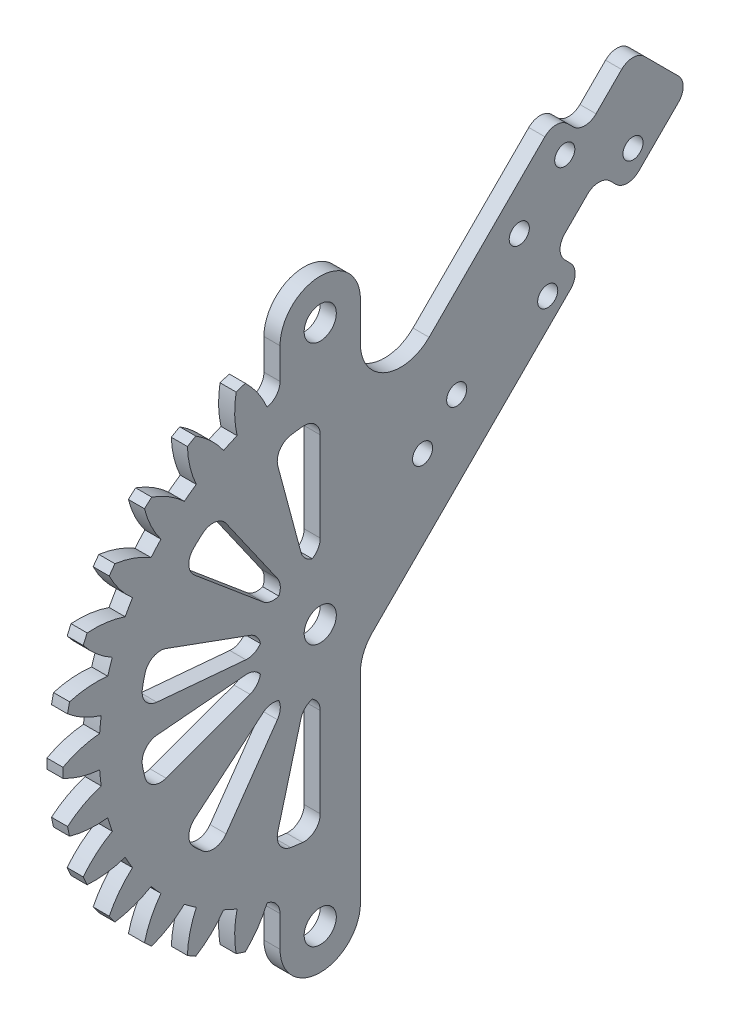
SolidWorks part; units mm, degrees
material "Thornel Mat VMA"
ref_plane "Plane1" through (0, 0, 0) normal (0, 0, 1) x (1, 0, 0)
ref_plane "Plane2" through (0, 0, 0) normal (0, 1, 0) x (1, 0, 0)
ref_plane "Plane3" through (0, 0, 0) normal (1, 0, 0) x (0, 0, -1)
sketch "HoldingSke" plane through (0, 0, 0) normal (0, 1, 0) x (1, 0, 0)
  line L0 (0, 0) -> (0.433, -0.25)
  line L1 (-15, 0) -> (100, 0) construction
  line L2 (0, 0) -> (-2.1039, 2.3779)
  line L3 (0, 0) -> (-11.863, 4.5341)
  line L4 (0, 0) -> (7.479, 4.318)
  line L5 (0, 0) -> (-46.8476, -17.4728)
  line L6 (0, 0) -> (-1.6579, -1.1186)
  line L7 (-2.1039, 2.3779) -> (8.6586, 51.2059)
  line L8 (-76.2, 54.61) -> (-76.1, 54.61)
  line L9 (-71.009, 38.7566) -> (-53.1078, 45.2721)
  line L10 (-76.2, 71.12) -> (104.1128, 71.12)
  line L11 (0, 0) -> (-2, 0)
  line L12 (-76.2, 101.6) -> (-76.133, 101.6)
  line L13 (24.9733, 27.94) -> (52.9518, 28.4284)
  line L14 (24.9733, 27.94) -> (24.9743, 27.94)
  line L15 (24.9733, 27.94) -> (100.4006, 29.5858)
  line L16 (-63.627, -2) -> (-12.827, -2)
  circle A0 centre (0, 0) radius 0.4
  circle A1 centre (0, 0) radius 27.499
  circle A2 centre (0, 0) radius 37.5
  circle A3 centre (0, 0) radius 0.4
  dimension "MHD" = 54.998
  dimension "Hub_dia" = 75
  dimension "Bore" = 0.8
  dimension "MBD" = 0.8
  dimension "Num_teeth" = 30
  dimension "Pitch" = 0.5
  dimension "Overall_len" = 50
  dimension "Show_teeth" = 30
  dimension "Thickness" = 2
  dimension "OAL" = 50.0001
  dimension "T_dim" = 0.1
  dimension "Ap" = 20
  dimension "H" = 19.05
  dimension "Pitch_radius" = 180.3128
  dimension "Width" = 2
  dimension "Backlash" = 0.067
  dimension "Addendum_fac" = 1
  dimension "Dedendum_fac" = 1.25
  dimension "Clearance_fac" = 0.25
  dimension "Dedendum_add" = 0.001
  dimension "Module" = 2
sketch "BasProSke" plane through (0, 0, 0) normal (0, 1, 0) x (1, 0, 0)
  line L0 (-10, 0) -> (60, 0) construction
  line L1 (0, 0) -> (0, 32)
  line L2 (0, 0) -> (2, 0)
  line L3 (2, 0) -> (2, 32)
  line L4 (2, 32) -> (0, 32)
  dimension "Thickness" = 2
  dimension "Diameter" = 64
revolve "Base-Revolve" add sketch "BasProSke" angle 360 about L0
sketch "TooCutSke" plane through (0, 0, 0) normal (1, 0, 0) x (0, 0, -1)
  line L1 (0, 0) -> (0, 107) construction
  line L2 (0, 0) -> (-1.6873, 29.9525) construction
  line L3 (0, 0) -> (-6.2643, 59.6013) construction
  line L4 (-1.6873, 29.9525) -> (-3.1322, 29.8007) construction
  arc A0 (0.9186, 27.4837) -> (-0.9186, 27.4837) centre (0, 0) ccw
  arc A1 (2.7618, 31.9061) -> (-2.7618, 31.9061) centre (0, 0) ccw
  circle A2 centre (0, 0) radius 30 construction
  circle A3 centre (0, 0) radius 28.1908 construction
  arc A4 (-0.9186, 27.4837) -> (-2.7618, 31.9061) centre (-12.6936, 25.1712) ccw
  arc A5 (2.7618, 31.9061) -> (0.9186, 27.4837) centre (12.6936, 25.1712) ccw
  dimension "Root_dia" = 54.998
  dimension "Overcut_dia" = 64.0508
  dimension "Pitch_dia" = 60
  dimension "Base_dia" = 56.3816
  dimension "Flank_rad" = 12
  dimension "Half_ang" = 6
  dimension "Half_CT" = 1.4528
extrude "ToothCut" cut sketch "TooCutSke" along normal through all
fillet "Breaks" [suppressed] radius 0.04 tangent propagation no
fillet "RootFillets" [suppressed] radius 0.501
pattern_circular "TeethCuts" count 30 every 12 about axis through (-10, 0, 0) along (1, 0, 0) of "ToothCut", "RootFillets", "Breaks"
sketch "HubNeaOneSke" plane through (0, 0, 0) normal (-1, 0, 0) x (0, 0, 1)
  circle A0 centre (0, 0) radius 27.499
  dimension "Diameter" = 54.998
extrude "HubNearOne" [suppressed] add sketch "HubNeaOneSke" along normal blind 48.0001
sketch "HubNeaBotSke" plane through (0, 0, 0) normal (-1, 0, 0) x (0, 0, 1)
  circle A0 centre (0, 0) radius 27.499
  dimension "Diameter" = 54.998
extrude "HubNearBoth" [suppressed] add sketch "HubNeaBotSke" along normal blind 24
ref_plane "FarPln" through (2, 0, 0) normal (1, 0, 0) x (0, 0, -1)
sketch "HubFarSke" plane through (2, 0, 0) normal (1, 0, 0) x (0, 0, -1)
  circle A0 centre (0, 0) radius 27.499
  dimension "Diameter" = 54.998
extrude "HubFar" [suppressed] add sketch "HubFarSke" along normal blind 24
sketch "BorSke" plane through (0, 0, 0) normal (1, 0, 0) x (0, 0, -1)
  circle A0 centre (0, 0) radius 0.4
  dimension "Diameter" = 0.8
extrude "Bore" cut sketch "BorSke" along normal mid plane 100.0001
sketch "KeySke" plane through (0, 0, 0) normal (1, 0, 0) x (0, 0, -1)
  line L0 (-0.05, 0) -> (-0.05, 0.5)
  line L1 (-0.05, 0.5) -> (0.05, 0.5)
  line L2 (0.05, 0.5) -> (0.05, 0)
  line L3 (0, 0) -> (0, 34) construction
  line L4 (-0.05, 0) -> (0.05, 0)
  dimension "Offset" = 0.5
  dimension "Width" = 0.1
extrude "Keyway" [suppressed] cut sketch "KeySke" along normal mid plane 100.0001
pattern_circular "Keyway2" [suppressed] count 2 every 90 about axis through (-10, 0, 0) along (1, 0, 0)
sketch "草图1" plane through (2, 0, 0) normal (1, 0, 0) x (0, 0, -1)
  line L0 (0, 36.7097) -> (0, -36.236)
  line L1 (0, -36.236) -> (49.7984, -32.8986)
  line L2 (49.7984, -32.8986) -> (48.3681, 29.8306)
  line L3 (48.3681, 29.8306) -> (0, 36.7097)
extrude "切除-拉伸1" cut sketch "草图1" against normal blind 10
sketch "草图2" plane through (2, 0, 0) normal (1, 0, 0) x (0, 0, -1)
  line L1 (-5.5508, 26.9329) -> (-6.8733, 33.3497)
  line L2 (-6.8733, 33.3497) -> (-0.6382, 34.2357)
  line L3 (-0.6382, 34.2357) -> (0, 27.499)
  line L4 (-5.7242, -26.8966) -> (-4.3967, -32.8332)
  line L5 (-4.3967, -32.8332) -> (-0.0637, -31.065)
  line L6 (-0.0637, -31.065) -> (0, -27.499)
  arc A0 (-5.7242, -26.8966) -> (0, -27.499) centre (0, 0) ccw
  arc A1 (0, 27.499) -> (-5.5508, 26.9329) centre (0, 0) ccw
extrude "切除-拉伸3" cut sketch "草图2" against normal through all
sketch "草图4" plane through (2, 0, 0) normal (1, 0, 0) x (0, 0, -1)
  line L0 (0, 27.499) -> (0, 0.4) construction
  line L1 (0, 27.499) -> (5, 27.499)
  line L2 (0, 27.499) -> (0, -27.499)
  line L3 (0, -27.499) -> (5, -27.499)
  line L4 (5, 27.499) -> (5, -27.499)
  arc A0 (0, 27.499) -> (-6.6127, 26.6921) centre (0, 0) ccw construction
  dimension "D1" = 5
  dimension "D2" = 54.998
extrude "凸台-拉伸1" add sketch "草图4" against normal up to surface (2 mm away) contours L1 L4 L3 L2 up to face at (0, 0, 19.8937)
sketch "草图5" plane through (2, 0, 0) normal (1, 0, 0) x (0, 0, -1)
  line L0 (0, 0.4) -> (0, -0.4) construction
  circle A0 centre (0, 0) radius 2
  dimension "D1" = 4
extrude "切除-拉伸4" cut sketch "草图5" against normal blind 10
sketch "草图6" plane through (2, 0, 0) normal (1, 0, 0) x (0, 0, -1)
  line L0 (0, 0) -> (0, 48.1595) construction
  line L1 (5, 27.499) -> (5, 32.499)
  line L2 (-5, 32.499) -> (-5, 27.0406)
  line L4 (0, 27.499) -> (5, 27.499) construction
  line L5 (0, 27.499) -> (5, 27.499)
  arc A0 (0, 27.499) -> (-6.6127, 26.6921) centre (0, 0) ccw construction
  arc A1 (5, 32.499) -> (-5, 32.499) centre (0, 32.499) ccw
  arc A2 (0, 27.499) -> (-5, 27.0406) centre (0, 0) ccw
  dimension "D1" = 5
extrude "凸台-拉伸2" add sketch "草图6" against normal blind 2
sketch "草图8" plane through (2, 0, 0) normal (1, 0, 0) x (0, 0, -1)
  circle A0 centre (0, 32.5) radius 2
  circle A2 centre (0, 0) radius 2 construction
  dimension "D1" = 4
  dimension "D2" = 32.5
extrude "切除-拉伸6" cut sketch "草图8" against normal blind 2
mirror "镜向2" about plane through (0, 0, 0) normal (0, 1, 0) of "凸台-拉伸2", "切除-拉伸6"
fillet "圆角2" radius 2 2 edges at (1, -27.0406, 5) (1, 27.0406, 5)
sketch "草图9" plane through (2, 0, 0) normal (1, 0, 0) x (0, 0, -1)
  line L0 (5, 15.6066) -> (35.3553, 45.9619)
  line L2 (5, 32.499) -> (5, -32.499) construction
  line L3 (5, -5.6066) -> (45.9619, 35.3553)
  line L4 (-80.3033, 5.3033) -> (-122.7297, -37.1231) construction
  line L5 (-80.3033, 5.3033) -> (-122.7297, -37.1231) construction
  line L6 (-112.1231, -47.7297) -> (-69.6967, -5.3033) construction
  line L7 (-112.1231, -47.7297) -> (-69.6967, -5.3033) construction
  line L8 (35.3553, 45.9619) -> (45.9619, 35.3553)
  line L9 (5, 15.6066) -> (5, -5.6066)
  line L10 (0, 0) -> (40.6586, 40.6586) construction
  circle A8 centre (12.7279, 12.0208) radius 1.25
  circle A9 centre (16.9706, 16.2635) radius 1.25
  circle A10 centre (12.7279, 12.0208) radius 1.35 construction
  circle A11 centre (16.9706, 16.2635) radius 1.35 construction
  dimension "D3" = 2.5
  dimension "D1" = 57.5
  dimension "D2" = 15
extrude "凸台-拉伸3" add sketch "草图9" against normal blind 2
fillet "圆角3" radius 5 2 edges at (1, -5.6066, -5) (1, 15.6066, -5)
sketch "草图10" plane through (2, 0, 0) normal (1, 0, 0) x (0, 0, -1)
  line L0 (32.215, 0) -> (-49.323, 0) construction
  line L1 (0, -7.5) -> (0, -22.5)
  line L2 (-1.9411, -7.2444) -> (-5.8234, -21.7333)
  line L3 (-4.3018, -6.1436) -> (-12.9055, -18.4309)
  line L4 (-5.7453, -4.8209) -> (-17.236, -14.4627)
  line L5 (-7.0477, -2.5652) -> (-21.1431, -7.6955)
  line L6 (-7.4715, -0.6537) -> (-22.4144, -1.961)
  line L7 (0, 0) -> (0, -22.5) construction
  line L8 (0, 0) -> (-12.9055, -18.4309) construction
  line L9 (0, 0) -> (-12.9055, 18.4309) construction
  line L10 (0, 0) -> (0, 22.5) construction
  line L11 (-7.4715, 0.6537) -> (-22.4144, 1.961)
  line L12 (-7.0477, 2.5652) -> (-21.1431, 7.6955)
  line L13 (-5.7453, 4.8209) -> (-17.236, 14.4627)
  line L14 (-4.3018, 6.1436) -> (-12.9055, 18.4309)
  line L15 (-1.9411, 7.2444) -> (-5.8234, 21.7333)
  line L16 (0, 7.5) -> (0, 22.5)
  arc A0 (-7.4715, -0.6537) -> (-7.0477, -2.5652) centre (0, 0) ccw
  arc A1 (-22.4144, -1.961) -> (-21.1431, -7.6955) centre (0, 0) ccw
  arc A2 (-5.7453, -4.8209) -> (-4.3018, -6.1436) centre (0, 0) ccw
  arc A3 (-17.236, -14.4627) -> (-12.9055, -18.4309) centre (0, 0) ccw
  arc A4 (-5.8234, -21.7333) -> (0, -22.5) centre (0, 0) ccw
  arc A5 (-1.9411, -7.2444) -> (0, -7.5) centre (0, 0) ccw
  arc A6 (-1.9411, 7.2444) -> (0, 7.5) centre (0, 0) cw
  arc A7 (-5.8234, 21.7333) -> (0, 22.5) centre (0, 0) cw
  arc A8 (-17.236, 14.4627) -> (-12.9055, 18.4309) centre (0, 0) cw
  arc A9 (-5.7453, 4.8209) -> (-4.3018, 6.1436) centre (0, 0) cw
  arc A10 (-22.4144, 1.961) -> (-21.1431, 7.6955) centre (0, 0) cw
  arc A11 (-7.4715, 0.6537) -> (-7.0477, 2.5652) centre (0, 0) cw
  dimension "D1" = 15
  dimension "D2" = 45
  dimension "D3" = 35
  dimension "D5" = 15
  dimension "D4" = 3
extrude "切除-拉伸7" cut sketch "草图10" against normal blind 10
fillet "圆角5" radius 2 24 edges at (1, -7.6955, 21.1431) (1, -1.961, 22.4144) (1, 6.1436, 4.3018) (1, 4.8209, 5.7453) (1, 14.4627, 17.236) (1, 18.4309, 12.9055) (1, -18.4309, 12.9055) (1, -14.4627, 17.236) (1, -4.8209, 5.7453) (1, -6.1436, 4.3018) (1, -7.2444, 1.9411) (1, -7.5, 0) (1, -22.5, 0) (1, -21.7333, 5.8234) (1, 7.5, 0) (1, 7.2444, 1.9411) (1, 21.7333, 5.8234) (1, 22.5, 0) (1, 2.5652, 7.0477) (1, 0.6537, 7.4715) (1, 1.961, 22.4144) (1, 7.6955, 21.1431) (1, -2.5652, 7.0477) (1, -0.6537, 7.4715)
sketch "草图13" plane through (2, 0, 0) normal (1, 0, 0) x (0, 0, -1)
  line L0 (6.4645, -4.1421) -> (45.9619, 35.3553) construction
  line L1 (45.9619, 35.3553) -> (35.3553, 45.9619) construction
  circle A0 centre (38.8909, 31.8198) radius 1.25
  circle A1 centre (28.2843, 21.2132) radius 1.25
  dimension "D1" = 2.5
  dimension "D2" = 2.5
  dimension "D3" = 2.5
  dimension "D4" = 7.5
  dimension "D5" = 15
extrude "切除-拉伸10" cut sketch "草图13" against normal blind 10
sketch "草图14" plane through (2, 0, 0) normal (1, 0, 0) x (0, 0, -1)
  line L0 (32.5269, 21.9203) -> (38.1838, 27.5772)
  line L1 (32.5269, 21.9203) -> (28.9914, 25.4558)
  line L2 (38.1838, 27.5772) -> (34.6482, 31.1127)
  line L3 (28.9914, 25.4558) -> (34.6482, 31.1127)
  line L4 (6.4645, -4.1421) -> (45.9619, 35.3553) construction
  line L5 (45.9619, 35.3553) -> (35.3553, 45.9619) construction
  dimension "D1" = 11
  dimension "D2" = 8
  dimension "D3" = 5
extrude "切除-拉伸11" cut sketch "草图14" against normal blind 10
sketch "草图12" plane through (2, 0, 0) normal (1, 0, 0) x (0, 0, -1)
  line L0 (35.3553, 45.9619) -> (38.8909, 42.4264)
  line L1 (35.3553, 45.9619) -> (29.3449, 39.9515)
  line L2 (38.8909, 42.4264) -> (32.8805, 36.416)
  line L3 (29.3449, 39.9515) -> (32.8805, 36.416)
  line L4 (45.9619, 35.3553) -> (35.3553, 45.9619) construction
  dimension "D1" = 8.5
  dimension "D2" = 5
extrude "切除-拉伸12" cut sketch "草图12" against normal blind 2
fillet "圆角7" radius 2 8 edges at (1, 35.3553, -45.9619) (1, 27.5772, -38.1838) (1, 31.1127, -34.6482) (1, 25.4558, -28.9914) (1, 21.9203, -32.5269) (1, 42.4264, -38.8909) (1, 36.416, -32.8805) (1, 39.9515, -29.3449)
sketch "草图16" plane through (2, 0, 0) normal (1, 0, 0) x (0, 0, -1)
  line L0 (27.9307, 38.5373) -> (13.5355, 24.1421) construction
  line L1 (30.7591, 38.5373) -> (31.4663, 37.8302) construction
  circle A0 centre (30.4056, 35.3553) radius 1.25
  circle A1 centre (24.7487, 29.6985) radius 1.25
  dimension "D1" = 2.5
  dimension "D2" = 4
  dimension "D3" = 4
  dimension "D4" = 8
  dimension "D5" = 2.5
extrude "切除-拉伸13" cut sketch "草图16" against normal blind 2
equation "' \"Module@HoldingSke\" = 6.35"
equation "' \"Num_teeth@HoldingSke\" = 12"
equation "' \"Ap@HoldingSke\" =  20"
equation "' \"Ap@HoldingSke\" = 20"
equation "' \"Width@HoldingSke\" = 0.5 * 25.4"
equation "' \"Hub_dia@HoldingSke\"= 1 * 25.4"
equation "' \"Hub_dia@HoldingSke\" = 1 * 25.4"
equation "' \"Overall_len@HoldingSke\" = 1.0 * 25.4"
equation "' \"Bore@HoldingSke\" = 0.75 * 25.4"
equation "' \"T_dim@HoldingSke\" = 0.1 * 25.4"
equation "' \"Width@KeySke\" = 0.25 * 25.4"
equation "' \"Show_teeth@HoldingSke\" = 13"
equation "' \"Backlash@HoldingSke\" = 0.009 * 25.4"
equation "' \"Addendum_fac@HoldingSke\" = 1.0"
equation "' \"Dedendum_fac@HoldingSke\" = 1.25"
equation "' \"Dedendum_add@HoldingSke\" = 0.00005 * 25.4"
equation "' \"Clearance_fac@HoldingSke\" = 0.25"
equation "\"Pitch@HoldingSke\" = 1 / \"Module@HoldingSke\""
equation "\"Overcut_dia@TooCutSke\" = (\"Num_teeth@HoldingSke\" + 2 * \"Addendum_fac@HoldingSke\") / \"Pitch@HoldingSke\" + 0.002 * 25.4"
equation "\"Pitch_dia@TooCutSke\" = \"Num_teeth@HoldingSke\" / \"Pitch@HoldingSke\""
equation "\"Base_dia@TooCutSke\" = \"Num_teeth@HoldingSke\" / \"Pitch@HoldingSke\" * cos((\"Ap@HoldingSke\"  * 3.14159265 / 180))"
equation "\"Root_dia@TooCutSke\" = (\"Num_teeth@HoldingSke\" + 2) / \"Pitch@HoldingSke\" - 2 * (\"Addendum_fac@HoldingSke\" + \"Dedendum_fac@HoldingSke\") / \"Pitch@HoldingSke\" - \"Dedendum_add@HoldingSke\" * 2"
equation "\"Half_ang@TooCutSke\" = 180 / \"Num_teeth@HoldingSke\""
equation "\"Half_CT@TooCutSke\" = \"Num_teeth@HoldingSke\" / \"Pitch@HoldingSke\" * sin((3.14159265 / 2 / \"Num_teeth@HoldingSke\")) / 2 - 7 * \"Backlash@HoldingSke\" / 4"
equation "\"Flank_rad@TooCutSke\" = \"Num_teeth@HoldingSke\" / \"Pitch@HoldingSke\" / 5"
equation "\"Radius@RootFillets\" = \"Clearance_fac@HoldingSke\" / \"Pitch@HoldingSke\" + \"Dedendum_add@HoldingSke\""
equation "\"Break_rad@Breaks\" = 0.02 / \"Pitch@HoldingSke\""
equation "\"Thickness@HoldingSke\" = \"Width@HoldingSke\""
equation "\"OAL@HoldingSke\" = \"Thickness@HoldingSke\""
equation "\"MHD@HoldingSke\" = (\"Num_teeth@HoldingSke\" + 2) / \"Pitch@HoldingSke\" - 2 * (\"Addendum_fac@HoldingSke\" + \"Dedendum_fac@HoldingSke\")  / \"Pitch@HoldingSke\" - \"Dedendum_add@HoldingSke\" * 2"
equation "\"MBD@HoldingSke\" = (\"Num_teeth@HoldingSke\" + 2) / \"Pitch@HoldingSke\" - 2 * (\"Addendum_fac@HoldingSke\" + \"Dedendum_fac@HoldingSke\")  / \"Pitch@HoldingSke\" - \"Dedendum_add@HoldingSke\" * 2 - 0.002 * 25.4"
equation "\"MHD@HoldingSke\" = ((sgn( \"MHD@HoldingSke\" - \"Hub_dia@HoldingSke\" )-1)*( \"MHD@HoldingSke\" - \"Hub_dia@HoldingSke\" ))/-2+ \"Hub_dia@HoldingSke\""
equation "\"MBD@HoldingSke\" = ((sgn( \"MBD@HoldingSke\" - \"Bore@HoldingSke\" )-1)*( \"MBD@HoldingSke\" - \"Bore@HoldingSke\" ))/-2+ \"Bore@HoldingSke\""
equation "\"OAL@HoldingSke\" = ((sgn( \"OAL@HoldingSke\" - \"Overall_len@HoldingSke\" )+1)*( \"OAL@HoldingSke\" - \"Overall_len@HoldingSke\" ))/2 + \"Overall_len@HoldingSke\" + 0.000002 * 25.4"
equation "\"Num_teeth@TeethCuts\" = int( \"Show_teeth@HoldingSke\" ) + 1"
equation "\"Num_teeth@TeethCuts\" = ((sgn( \"Num_teeth@TeethCuts\" - \"Num_teeth@HoldingSke\" )-1)*( \"Num_teeth@TeethCuts\" - \"Num_teeth@HoldingSke\" ))/-2+ \"Num_teeth@HoldingSke\""
equation "\"Num_teeth@TeethCuts\" = ((sgn( \"Num_teeth@TeethCuts\" - 2.0)+1)*( \"Num_teeth@TeethCuts\" - 2.0))/2 +2.0"
equation "\"Angle@TeethCuts\" = 360.0 / \"Num_teeth@HoldingSke\""
equation "\"Diameter@BasProSke\" = (\"Num_teeth@HoldingSke\" + 2 * \"Addendum_fac@HoldingSke\") / \"Pitch@HoldingSke\""
equation "\"Thickness@BasProSke\"  = \"Thickness@HoldingSke\""
equation "' \"Fillet_rad@BasProSke\" =  \"Thickness@HoldingSke\" * 0.05"
equation "' \"Fillet_rad@BasProSke\" = \"Thickness@HoldingSke\" * 0.05"
equation "\"MHD@HoldingSke\" = ((sgn( \"MHD@HoldingSke\" - \"Root_dia@TooCutSke\" )-1)*( \"MHD@HoldingSke\" - \"Root_dia@TooCutSke\" ))/-2+ \"Root_dia@TooCutSke\""
equation "\"Diameter@HubNeaOneSke\" = \"MHD@HoldingSke\""
equation "\"Length@HubNearOne\" = \"OAL@HoldingSke\" - \"Thickness@BasProSke\""
equation "\"Diameter@HubNeaBotSke\" = \"MHD@HoldingSke\""
equation "\"Length@HubNearBoth\" = ( \"OAL@HoldingSke\" - \"Thickness@BasProSke\" ) / 2.0"
equation "\"Thickness@FarPln\" = \"Thickness@BasProSke\""
equation "\"Diameter@HubFarSke\" = \"MHD@HoldingSke\""
equation "\"Length@HubFar\" = ( \"OAL@HoldingSke\" - \"Thickness@BasProSke\" ) / 2.0"
equation "\"Diameter@BorSke\" = \"MBD@HoldingSke\""
equation "\"D1@Bore\" = \"OAL@HoldingSke\" * 2.0"
equation "\"D1@Keyway\" = \"OAL@HoldingSke\" * 2.0"
equation "\"Offset@KeySke\" = \"T_dim@HoldingSke\" + \"MBD@HoldingSke\" / 2.0"
